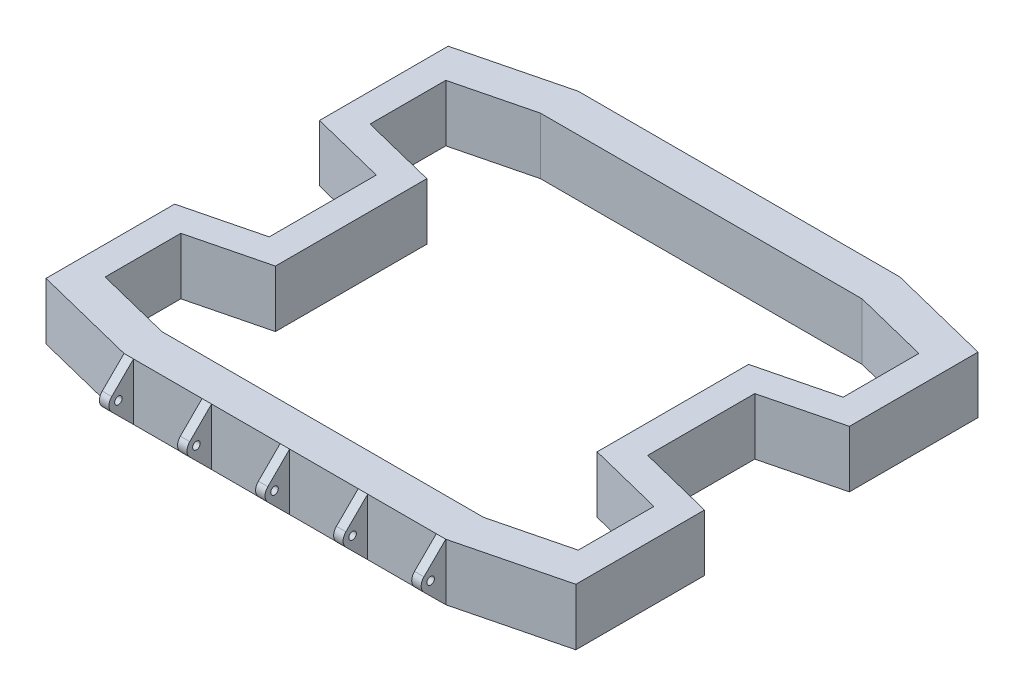
SolidWorks part; units mm, degrees
ref_plane "Front Plane" through (0, 0, 0) normal (0, 0, 1) x (1, 0, 0)
ref_plane "Top Plane" through (0, 0, 0) normal (0, 1, 0) x (1, 0, 0)
ref_plane "Right Plane" through (0, 0, 0) normal (1, 0, 0) x (0, 0, -1)
sketch "Sketch1" plane through (0, 0, 0) normal (0, 1, 0) x (1, 0, 0)
  line L0 (-69.85, 175.6262) -> (-19.05, 162.9262)
  line L1 (0, 0) -> (215.9, 0) construction
  line L2 (0, 0) -> (0, 254) construction
  line L3 (0, 254) -> (215.9, 254) construction
  line L4 (215.9, 0) -> (215.9, 254) construction
  line L5 (-69.85, 175.6262) -> (-69.85, 261.9375)
  line L6 (-69.85, 261.9375) -> (0, 279.4)
  line L7 (0, 177.8) -> (0, 76.2)
  line L8 (0, 177.8) -> (-50.8, 190.5)
  line L9 (-50.8, 190.5) -> (-50.8, 241.3)
  line L10 (-50.8, 241.3) -> (0, 254)
  line L11 (-19.05, 162.9262) -> (-19.05, 91.0738)
  line L12 (0, 254) -> (215.9, 254)
  line L13 (0, 279.4) -> (215.9, 279.4)
  line L14 (107.95, 254) -> (107.95, 0) construction
  line L15 (0, 127) -> (215.9, 127) construction
  line L16 (234.95, 162.9262) -> (234.95, 91.0738)
  line L17 (266.7, 241.3) -> (215.9, 254)
  line L18 (215.9, 177.8) -> (266.7, 190.5)
  line L19 (215.9, 177.8) -> (215.9, 76.2)
  line L20 (285.75, 261.9375) -> (215.9, 279.4)
  line L21 (266.7, 190.5) -> (266.7, 241.3)
  line L22 (285.75, 175.6262) -> (285.75, 261.9375)
  line L23 (285.75, 175.6262) -> (234.95, 162.9262)
  line L24 (0, 0) -> (215.9, 0) construction
  line L25 (285.75, 78.3738) -> (234.95, 91.0738)
  line L26 (285.75, 78.3738) -> (285.75, -7.9375)
  line L27 (266.7, 63.5) -> (266.7, 12.7)
  line L28 (285.75, -7.9375) -> (215.9, -25.4)
  line L29 (215.9, 76.2) -> (266.7, 63.5)
  line L30 (266.7, 12.7) -> (215.9, 0)
  line L31 (0, -25.4) -> (215.9, -25.4)
  line L32 (0, 0) -> (215.9, 0)
  line L33 (-50.8, 12.7) -> (0, 0)
  line L34 (-50.8, 63.5) -> (-50.8, 12.7)
  line L35 (0, 76.2) -> (-50.8, 63.5)
  line L36 (-69.85, -7.9375) -> (0, -25.4)
  line L37 (-69.85, 78.3738) -> (-69.85, -7.9375)
  line L38 (-69.85, 78.3738) -> (-19.05, 91.0738)
  point P5 (-50.8, 215.9)
  point P9 (0, 127)
  point P13 (107.95, 254)
  point P22 (107.95, 279.4)
  point P28 (215.9, 127)
  point P30 (266.7, 215.9)
  point P38 (234.95, 127)
  point P40 (-19.05, 127)
  point P45 (266.7, 38.1)
  point P46 (107.95, -25.4)
  point P47 (107.95, 0)
  point P48 (-50.8, 38.1)
  dimension "D1" = 254
  dimension "D2" = 215.9
  dimension "D3" = 50.8
  dimension "D4" = 50.8
  dimension "D5" = 38.1
  dimension "D6" = 19.05
  dimension "D7" = 19.05
  dimension "D8" = 25.4
extrude "Boss-Extrude1" add sketch "Sketch1" along normal blind 38.1
sketch "Sketch2" plane through (0, 0, 0) normal (1, 0, 0) x (0, 0, -1)
  line L0 (-40.0362, 23.554) -> (-25.4, 38.1)
  line L1 (-40.0362, 14.546) -> (-25.4, 0)
  line L2 (-25.4, 0) -> (-25.4, 38.1)
  circle A0 centre (-35.56, 19.05) radius 2.54
  arc A1 (-40.0362, 23.554) -> (-40.0362, 14.546) centre (-35.56, 19.05) ccw
  point P2 (0, 0)
  point P10 (-25.4, 19.05)
  dimension "D1" = 3.81
  dimension "D2" = 5.08
  dimension "D3" = 10.16
extrude "Boss-Extrude2" add sketch "Sketch2" along normal blind 6.35
pattern_linear "LPattern1" count 5 spacing 52.3875 along (1, 0, 0) of "Boss-Extrude2"
